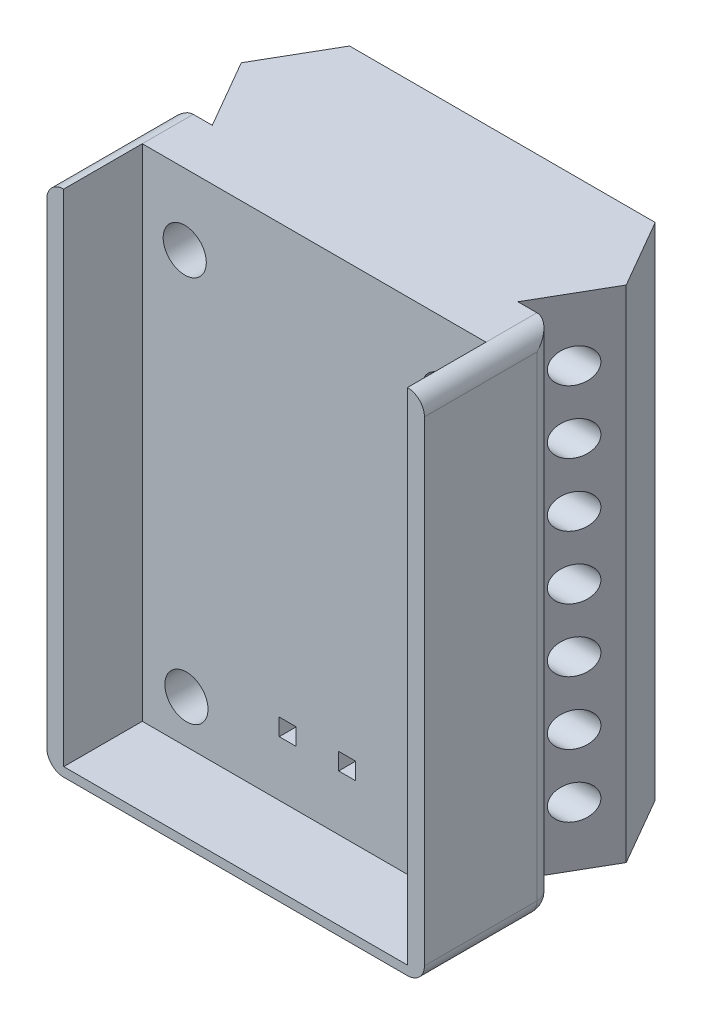
SolidWorks part; units mm, degrees
ref_plane "Front Plane" through (0, 0, 0) normal (0, 0, 1) x (1, 0, 0)
ref_plane "Top Plane" through (0, 0, 0) normal (0, 1, 0) x (1, 0, 0)
ref_plane "Right Plane" through (0, 0, 0) normal (1, 0, 0) x (0, 0, -1)
sketch "Sketch1" plane through (0, 0, 0) normal (0, 0, 1) x (1, 0, 0)
  line L1 (-1.0902, 29.4597) -> (21.1519, 29.4597)
  line L2 (-1.0902, 29.4597) -> (-1.0902, -0.5403)
  line L3 (-1.0902, -0.5403) -> (21.1519, -0.5403)
  line L4 (21.1519, 29.4597) -> (21.1519, -0.5403)
  circle A1 centre (2.4098, 25.2831) radius 1.27
  circle A2 centre (17.6519, 25.2831) radius 1.27
  circle A3 centre (2.5098, 2.5468) radius 1.27
  circle A4 centre (17.7519, 2.5468) radius 1.27
  point P8 (0, 0)
  dimension "D4" = 2.54
  dimension "D5" = 2.54
  dimension "D6" = 3.5
  dimension "D1" = 2.54
  dimension "D7" = 2.54
  dimension "D2" = 3.6
  dimension "D3" = 3.5
  dimension "D8" = 3.4
sketch "Sketch3" plane through (0, 0, 0) normal (0, 0, 1) x (1, 0, 0)
  line L1 (12.4762, 4.2504) -> (11.4762, 4.2504)
  line L2 (12.4762, 4.2504) -> (12.4762, 3.2504)
  line L3 (12.4762, 3.2504) -> (11.4762, 3.2504)
  line L4 (11.4762, 4.2504) -> (11.4762, 3.2504)
  line L5 (8.9762, 4.2504) -> (7.9762, 4.2504)
  line L6 (8.9762, 4.2504) -> (8.9762, 3.2504)
  line L7 (8.9762, 3.2504) -> (7.9762, 3.2504)
  line L8 (7.9762, 4.2504) -> (7.9762, 3.2504)
  dimension "D1" = 1
  dimension "D2" = 1
  dimension "D3" = 1
  dimension "D4" = 1
  dimension "D5" = 2.5
  dimension "D6" = 7.9762
  dimension "D7" = 3.2504
extrude "Boss-Extrude1" add sketch "Sketch1" along normal blind 13 and the other way blind 3 contours L2 L3 L4 L1
sketch "Sketch4" plane through (0, 0, 0) normal (0, 1, 0) x (1, 0, 0)
  line L0 (-1.0902, 3) -> (-1.0902, -13) construction
  line L1 (-0.0902, 0) -> (20.1519, 0)
  line L2 (-0.0902, 0) -> (-0.0902, -12)
  line L3 (-0.0902, -12) -> (20.1519, -12)
  line L4 (20.1519, 0) -> (20.1519, -12)
  line L5 (-1.0902, 3) -> (21.1519, 3) construction
  line L6 (21.1519, 3) -> (21.1519, -13) construction
  line L7 (-1.0902, -13) -> (21.1519, -13) construction
  dimension "D1" = 1
  dimension "D2" = 3
  dimension "D3" = 1
  dimension "D4" = 1
extrude "Cut-Extrude1" cut sketch "Sketch4" along normal blind 33
extrude "Cut-Extrude2" cut sketch "Sketch3" against normal blind 2.1
sketch "Sketch6" plane through (0, 0, -3) normal (0, 0, -1) x (-1, 0, 0)
  circle A0 centre (-17.6519, 25.2831) radius 1.27
  circle A1 centre (-2.4098, 25.2831) radius 1.27
  circle A2 centre (-17.7519, 2.5468) radius 1.27
  circle A3 centre (-2.5098, 2.5468) radius 1.27
extrude "Cut-Extrude3" cut sketch "Sketch6" against normal blind 3.1 contours A2 | A3 | A1 | A0
sketch "Sketch7" plane through (0, 0, 0) normal (0, 1, 0) x (1, 0, 0)
  line L0 (1.0308, 3) -> (19.0308, 3)
  line L1 (1.0308, 3) -> (-1.3042, 7.0443)
  line L2 (-1.3042, 7.0443) -> (1.0308, 11.0887)
  line L3 (1.0308, 11.0887) -> (19.0308, 11.0887)
  line L4 (19.0308, 11.0887) -> (21.3658, 7.0443)
  line L5 (21.3658, 7.0443) -> (19.0308, 3)
  line L6 (-1.0902, 3) -> (21.1519, 3) construction
  point P2 (6.9408, 15.4175)
  point P7 (10.0308, 3)
  dimension "D1" = 18
  dimension "D2" = 120
  dimension "D3" = 120
  dimension "D4" = 4.67
  dimension "D5" = 120
extrude "Boss-Extrude3" add sketch "Sketch7" along normal up to surface (29.4597 mm away) up to face at (10.0308, 29.4597, 5)
sketch "Sketch8" plane through (0, 0, 0) normal (1, 0, 0) x (0, 0, -1)
  line L0 (7.0443, 29.4597) -> (3, 29.4597) construction
  line L1 (3, 29.4597) -> (3, -0.5403) construction
  circle A0 centre (5.1, 25.7497) radius 1
  dimension "D2" = 2
  dimension "D1" = 3.71
  dimension "D3" = 2.1
extrude "Cut-Extrude4" cut sketch "Sketch8" along normal through all both and the other way through all
pattern_linear "LPattern1" count 7 spacing 3.71 along (0, -1, 0) of "Cut-Extrude4"
fillet "Fillet2" radius 1 11 edges at (10.0308, -0.5403, -3) (10.0308, -0.5403, 13) (-1.0902, 14.4597, -3) (-1.0902, 29.4597, 5) (-1.0902, 14.4597, 13) (-1.0902, -0.5403, 5) (21.1519, 14.4597, -3) (21.1519, -0.5403, 5) (21.1519, 14.4597, 13) (21.1519, 29.4597, 5) (10.0308, 29.4597, 13)
sketch "Sketch9" plane through (0, 0, 0) normal (0, 1, 0) x (1, 0, 0)
  line L1 (27.8788, -16.7666) -> (-6.1228, -16.7666)
  line L2 (27.8788, -16.7666) -> (27.8788, -4.6251)
  line L3 (27.8788, -4.6251) -> (-6.1228, -4.6251)
  line L4 (-6.1228, -16.7666) -> (-6.1228, -4.6251)
extrude "OptionalCut" cut sketch "Sketch9" along normal through all both and the other way through all
